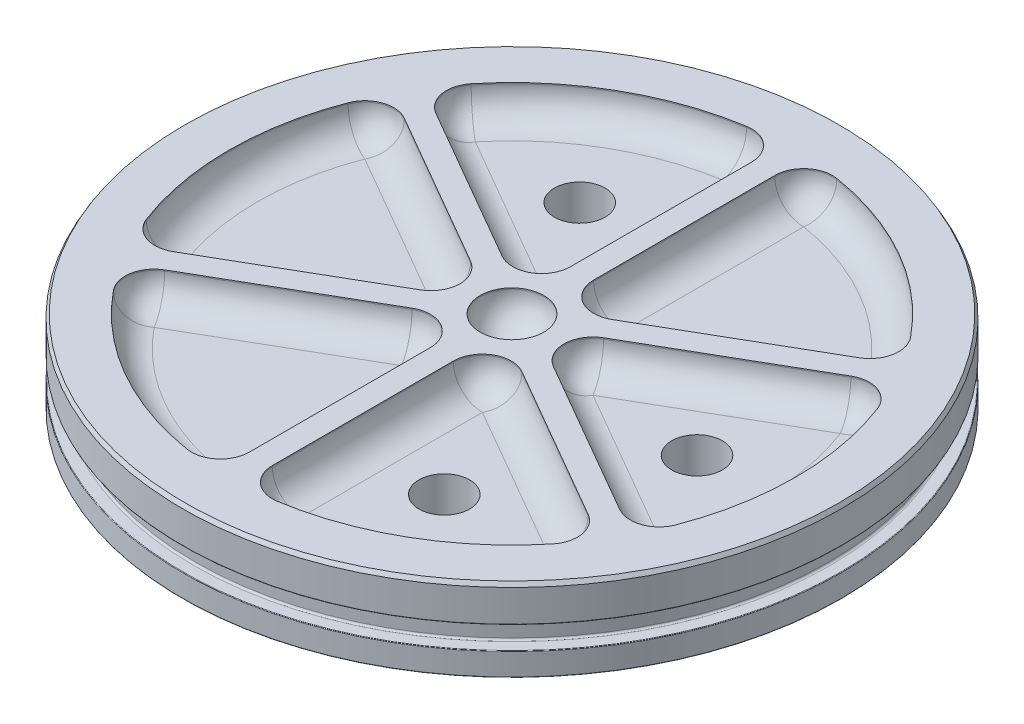
SolidWorks part; units mm, degrees
material "6061-T6 (SS)"
ref_plane "Front Plane" through (0, 0, 0) normal (0, 0, 1) x (1, 0, 0)
ref_plane "Top Plane" through (0, 0, 0) normal (0, 1, 0) x (1, 0, 0)
ref_plane "Right Plane" through (0, 0, 0) normal (1, 0, 0) x (0, 0, -1)
sketch "Sketch1" plane through (0, 0, 0) normal (0, 0, 1) x (1, 0, 0)
  line L0 (0, 48.1922) -> (0, -25.6743) construction
  line L1 (0, 0) -> (72.39, 0)
  line L2 (72.39, 0) -> (72.39, 5.08)
  line L3 (72.39, 5.08) -> (69.469, 5.08)
  line L4 (69.469, 5.08) -> (69.469, 10.0584)
  line L5 (69.469, 10.0584) -> (72.39, 10.0584)
  line L6 (72.39, 10.0584) -> (72.39, 18.034)
  line L7 (72.39, 18.034) -> (62.23, 18.034)
  line L8 (62.23, 18.034) -> (62.23, 11.43)
  line L9 (62.23, 11.43) -> (0, 11.43)
  line L10 (0, 11.43) -> (0, 0)
  dimension "D1" = 144.78
  dimension "D2" = 4.9784
  dimension "D3" = 2.921
  dimension "D5" = 11.43
  dimension "D6" = 10.16
  dimension "D4" = 18.034
  dimension "D7" = 5.08
revolve "Revolve1" add sketch "Sketch1" angle 360 about L0
sketch "Sketch6" plane through (0, 0, 0) normal (0, -1, 0) x (1, 0, 0)
  circle A0 centre (0, 0) radius 65.405
  dimension "D1" = 130.81
extrude "Boss-Extrude1" add sketch "Sketch6" along normal blind 2.54
hole_wizard "Pipe Tap Drill for 1/4 Tap - GN2" positions "Sketch2" profile "Sketch3" hole size "1/4" standard "ANSI Inch" end condition through all
sketch "Sketch2" plane through (0, 11.43, 0) normal (0, 1, 0) x (1, 0, 0)
  line L3 (-20.32, 35.1953) -> (0, 0) construction
  line L4 (0, 0) -> (40.64, 0) construction
  line L6 (0, 0) -> (20.32, -35.1953) construction
  line L7 (0, 0) -> (0, 62.23) construction
  line L8 (0, 0) -> (0, -62.23) construction
  circle A0 centre (0, 0) radius 62.23 construction
  circle A1 centre (0, 0) radius 62.23 construction
  point P41 (20.32, -35.1953)
  point P44 (-20.32, 35.1953)
  point P47 (40.64, 0)
  dimension "D1" = 40.64
  dimension "D2" = 40.64
  dimension "D3" = 40.64
  dimension "D4" = 30
  dimension "D5" = 30
sketch "Sketch3" plane through (20.32, 11.43, 35.1953) normal (1, 0, 0) x (0, 0, 1)
  line L0 (0, 0) -> (0, 13.97)
  line L1 (0, 13.97) -> (5.5626, 13.97)
  line L2 (5.5626, 13.97) -> (5.5626, 0)
  line L5 (5.5626, 0) -> (0, 0)
  line L11 (0, -6.35) -> (0, 107.95) construction
  dimension "Thru Hole Dia." = 11.1252
  dimension "Thru Hole Depth" = 13.97
fillet "CNC ID Fillet" radius 0.4064 3 edges at (-69.469, 10.0584, 0) (-69.469, 5.08, 0) (65.405, 0, 0)
fillet "CNC OD Fillet" radius 0.127 4 edges at (-72.39, 10.0584, 0) (-72.39, 5.08, 0) (65.405, -2.54, 0) (-72.39, 0, 0)
chamfer "CNC Chamfers" distance 0.508 angle 60 1 edges at (-72.39, 18.034, 0) first distance on face at (-62.23, 18.034, 0)
sketch "Sketch7" plane through (0, 18.034, 0) normal (0, 1, 0) x (1, 0, 0)
  line L0 (0, 0) -> (53.8928, -31.115) construction
  line L1 (0, 0) -> (0, -62.23) construction
  line L2 (0, 0) -> (-53.8928, -31.115) construction
  line L3 (0, 0) -> (-53.8928, 31.115) construction
  line L4 (0, 0) -> (0, 62.23) construction
  line L5 (0, 0) -> (53.8928, 31.115) construction
  line L6 (2.54, 15.3979) -> (2.54, 62.23)
  line L7 (-12.065, 9.8987) -> (-52.6228, 33.3147)
  line L8 (-14.605, -5.4993) -> (-55.1628, -28.9153)
  line L9 (-2.54, -15.3979) -> (-2.54, -62.23)
  line L10 (12.065, -9.8987) -> (52.6228, -33.3147)
  line L11 (14.605, 5.4993) -> (55.1628, 28.9153)
  line L12 (-2.54, 15.3979) -> (-2.54, 62.23)
  line L13 (-14.605, 5.4993) -> (-55.1628, 28.9153)
  line L14 (-12.065, -9.8987) -> (-52.6228, -33.3147)
  line L15 (2.54, -15.3979) -> (2.54, -62.23)
  line L16 (14.605, -5.4993) -> (55.1628, -28.9153)
  line L17 (12.065, 9.8987) -> (52.6228, 33.3147)
  line L18 (2.54, 0) -> (2.54, 62.23) construction
  line L19 (-1.27, 2.1997) -> (52.6228, 33.3147) construction
  line L20 (1.27, -2.1997) -> (55.1628, 28.9153) construction
  line L21 (1.27, 2.1997) -> (55.1628, -28.9153) construction
  line L22 (-1.27, -2.1997) -> (52.6228, -33.3147) construction
  line L23 (2.54, 0) -> (2.54, -62.23) construction
  line L24 (-2.54, 0) -> (-2.54, -62.23) construction
  line L25 (1.27, -2.1997) -> (-52.6228, -33.3147) construction
  line L26 (-1.27, 2.1997) -> (-55.1628, -28.9153) construction
  line L27 (-1.27, -2.1997) -> (-55.1628, 28.9153) construction
  line L28 (1.27, 2.1997) -> (-52.6228, 33.3147) construction
  line L29 (-2.54, 0) -> (-2.54, 62.23) construction
  line L30 (0, 0) -> (-62.23, 0) construction
  circle A0 centre (0, 0) radius 62.23 construction
  circle A1 centre (0, 0) radius 62.23
  arc A2 (2.54, 15.3979) -> (12.065, 9.8987) centre (8.89, 15.3979) ccw
  arc A3 (14.605, 5.4993) -> (14.605, -5.4993) centre (17.78, 0) ccw
  arc A4 (12.065, -9.8987) -> (2.54, -15.3979) centre (8.89, -15.3979) ccw
  arc A5 (-2.54, -15.3979) -> (-12.065, -9.8987) centre (-8.89, -15.3979) ccw
  arc A6 (-14.605, -5.4993) -> (-14.605, 5.4993) centre (-17.78, 0) ccw
  arc A7 (-12.065, 9.8987) -> (-2.54, 15.3979) centre (-8.89, 15.3979) ccw
  circle A9 centre (0, 0) radius 6.985
  point P11 (0, 0)
  circle M5 centre (0, 0) radius 62.23
  dimension "D4" = 6.35
  dimension "D6" = 13.97
  dimension "D5" = 30
  dimension "D2" = 2.54
  dimension "D3" = 2.54
  dimension "D1" = 6
extrude "Boss-Extrude2" add sketch "Sketch7" against normal up to surface (6.604 mm away) contours A7 L7 L13 A6 L8 L14 A5 L9 L15 A4 L10 L16 A3 L11 L17 A2 L6 L12 M5 region at (4.8837, 18.034, -8.4588) up to face at (20.32, 11.43, 40.7579)
fillet "Fillet1" radius 6.35 37 edges at (32.3214, 11.43, 21.5937) (5.715, 11.43, 9.8987) (34.8614, 11.43, -17.1943) (11.43, 11.43, 0) (-32.3214, 11.43, -21.5937) (-5.715, 11.43, -9.8987) (-5.715, 11.43, 9.8987) (-2.54, 11.43, 38.788) (-31.115, 11.43, 53.8928) (-32.3214, 11.43, 21.5937) (-11.43, 11.43, 0) (-34.8614, 11.43, 17.1943) (-62.23, 11.43, 0) (-34.8614, 11.43, -17.1943) (5.715, 11.43, -9.8987) (2.54, 11.43, -38.788) (31.115, 11.43, -53.8928) (32.3214, 11.43, -21.5937) (52.5779, 14.732, 33.2888) (2.54, 14.732, 62.1781) (31.115, 11.43, 53.8928) (2.54, 11.43, 38.788) (62.23, 11.43, 0) (34.8614, 11.43, 17.1943) (55.1179, 14.732, 28.8894) (55.1179, 14.732, -28.8894) (52.5779, 14.732, -33.2888) (2.54, 14.732, -62.1781) (-2.54, 14.732, 62.1781) (-52.5779, 14.732, 33.2888) (-55.1179, 14.732, 28.8894) (-52.5779, 14.732, -33.2888) (-2.54, 11.43, -38.788) (-2.54, 14.732, -62.1781) (-31.115, 11.43, -53.8928) (-55.1179, 14.732, -28.8894) (6.985, 11.43, 0)
sketch "Sketch8" plane through (0, -2.54, 0) normal (0, -1, 0) x (1, 0, 0)
  line L2 (-49.0472, -25.3844) -> (-14.605, -5.4993)
  line L3 (-14.605, 5.4993) -> (-49.0472, 25.3844)
  line L4 (-49.0472, -25.3844) -> (-14.605, -5.4993)
  line L5 (-14.605, 5.4993) -> (-49.0472, 25.3844)
  line L6 (-2.54, 15.3979) -> (-2.54, 55.1683)
  line L7 (-46.5072, 29.7839) -> (-12.065, 9.8987)
  line L8 (-2.54, 15.3979) -> (-2.54, 55.1683)
  line L9 (-46.5072, 29.7839) -> (-12.065, 9.8987)
  line L10 (12.065, 9.8987) -> (46.5072, 29.7839)
  line L11 (2.54, 55.1683) -> (2.54, 15.3979)
  line L12 (12.065, 9.8987) -> (46.5072, 29.7839)
  line L13 (2.54, 55.1683) -> (2.54, 15.3979)
  line L14 (14.605, -5.4993) -> (49.0472, -25.3844)
  line L15 (49.0472, 25.3844) -> (14.605, 5.4993)
  line L16 (14.605, -5.4993) -> (49.0472, -25.3844)
  line L17 (49.0472, 25.3844) -> (14.605, 5.4993)
  line L18 (2.54, -15.3979) -> (2.54, -55.1683)
  line L19 (46.5072, -29.7839) -> (12.065, -9.8987)
  line L20 (2.54, -15.3979) -> (2.54, -55.1683)
  line L21 (46.5072, -29.7839) -> (12.065, -9.8987)
  line L22 (-12.065, -9.8987) -> (-46.5072, -29.7839)
  line L23 (-2.54, -55.1683) -> (-2.54, -15.3979)
  line L24 (-12.065, -9.8987) -> (-46.5072, -29.7839)
  line L25 (-2.54, -55.1683) -> (-2.54, -15.3979)
  circle A0 centre (0, 0) radius 6.985 construction
  circle A1 centre (0, 0) radius 65.278
  circle A3 centre (0, 0) radius 6.985
  circle A5 centre (0, 0) radius 65.278
  arc A6 (-58.1565, 22.1449) -> (-58.1565, -22.1449) centre (0, 0) ccw
  arc A7 (-58.1565, -22.1449) -> (-49.0472, -25.3844) centre (-52.2222, -19.8852) ccw
  arc A8 (-14.605, -5.4993) -> (-14.605, 5.4993) centre (-17.78, 0) ccw
  arc A9 (-49.0472, 25.3844) -> (-58.1565, 22.1449) centre (-52.2222, 19.8852) ccw
  arc A10 (-58.1565, 22.1449) -> (-58.1565, -22.1449) centre (0, 0) ccw
  arc A11 (-58.1565, -22.1449) -> (-49.0472, -25.3844) centre (-52.2222, -19.8852) ccw
  arc A12 (-14.605, -5.4993) -> (-14.605, 5.4993) centre (-17.78, 0) ccw
  arc A13 (-49.0472, 25.3844) -> (-58.1565, 22.1449) centre (-52.2222, 19.8852) ccw
  arc A14 (-2.54, 55.1683) -> (-9.9002, 61.4374) centre (-8.89, 55.1683) ccw
  arc A15 (-9.9002, 61.4374) -> (-48.2563, 39.2926) centre (0, 0) ccw
  arc A16 (-48.2563, 39.2926) -> (-46.5072, 29.7839) centre (-43.3322, 35.2831) ccw
  arc A17 (-12.065, 9.8987) -> (-2.54, 15.3979) centre (-8.89, 15.3979) ccw
  arc A18 (-2.54, 55.1683) -> (-9.9002, 61.4374) centre (-8.89, 55.1683) ccw
  arc A19 (-9.9002, 61.4374) -> (-48.2563, 39.2926) centre (0, 0) ccw
  arc A20 (-48.2563, 39.2926) -> (-46.5072, 29.7839) centre (-43.3322, 35.2831) ccw
  arc A21 (-12.065, 9.8987) -> (-2.54, 15.3979) centre (-8.89, 15.3979) ccw
  arc A22 (46.5072, 29.7839) -> (48.2563, 39.2926) centre (43.3322, 35.2831) ccw
  arc A23 (48.2563, 39.2926) -> (9.9002, 61.4374) centre (0, 0) ccw
  arc A24 (9.9002, 61.4374) -> (2.54, 55.1683) centre (8.89, 55.1683) ccw
  arc A25 (2.54, 15.3979) -> (12.065, 9.8987) centre (8.89, 15.3979) ccw
  arc A26 (46.5072, 29.7839) -> (48.2563, 39.2926) centre (43.3322, 35.2831) ccw
  arc A27 (48.2563, 39.2926) -> (9.9002, 61.4374) centre (0, 0) ccw
  arc A28 (9.9002, 61.4374) -> (2.54, 55.1683) centre (8.89, 55.1683) ccw
  arc A29 (2.54, 15.3979) -> (12.065, 9.8987) centre (8.89, 15.3979) ccw
  arc A30 (49.0472, -25.3844) -> (58.1565, -22.1449) centre (52.2222, -19.8852) ccw
  arc A31 (58.1565, -22.1449) -> (58.1565, 22.1449) centre (0, 0) ccw
  arc A32 (58.1565, 22.1449) -> (49.0472, 25.3844) centre (52.2222, 19.8852) ccw
  arc A33 (14.605, 5.4993) -> (14.605, -5.4993) centre (17.78, 0) ccw
  arc A34 (49.0472, -25.3844) -> (58.1565, -22.1449) centre (52.2222, -19.8852) ccw
  arc A35 (58.1565, -22.1449) -> (58.1565, 22.1449) centre (0, 0) ccw
  arc A36 (58.1565, 22.1449) -> (49.0472, 25.3844) centre (52.2222, 19.8852) ccw
  arc A37 (14.605, 5.4993) -> (14.605, -5.4993) centre (17.78, 0) ccw
  arc A38 (2.54, -55.1683) -> (9.9002, -61.4374) centre (8.89, -55.1683) ccw
  arc A39 (9.9002, -61.4374) -> (48.2563, -39.2926) centre (0, 0) ccw
  arc A40 (48.2563, -39.2926) -> (46.5072, -29.7839) centre (43.3322, -35.2831) ccw
  arc A41 (12.065, -9.8987) -> (2.54, -15.3979) centre (8.89, -15.3979) ccw
  arc A42 (2.54, -55.1683) -> (9.9002, -61.4374) centre (8.89, -55.1683) ccw
  arc A43 (9.9002, -61.4374) -> (48.2563, -39.2926) centre (0, 0) ccw
  arc A44 (48.2563, -39.2926) -> (46.5072, -29.7839) centre (43.3322, -35.2831) ccw
  arc A45 (12.065, -9.8987) -> (2.54, -15.3979) centre (8.89, -15.3979) ccw
  arc A46 (-46.5072, -29.7839) -> (-48.2563, -39.2926) centre (-43.3322, -35.2831) ccw
  arc A47 (-48.2563, -39.2926) -> (-9.9002, -61.4374) centre (0, 0) ccw
  arc A48 (-9.9002, -61.4374) -> (-2.54, -55.1683) centre (-8.89, -55.1683) ccw
  arc A49 (-2.54, -15.3979) -> (-12.065, -9.8987) centre (-8.89, -15.3979) ccw
  arc A50 (-46.5072, -29.7839) -> (-48.2563, -39.2926) centre (-43.3322, -35.2831) ccw
  arc A51 (-48.2563, -39.2926) -> (-9.9002, -61.4374) centre (0, 0) ccw
  arc A52 (-9.9002, -61.4374) -> (-2.54, -55.1683) centre (-8.89, -55.1683) ccw
  arc A53 (-2.54, -15.3979) -> (-12.065, -9.8987) centre (-8.89, -15.3979) ccw
  dimension "D1" = 0
  dimension "D2" = 0
  dimension "D3" = 0
  dimension "D4" = 0
  dimension "D5" = 0
  dimension "D6" = 0
  dimension "D7" = 0
extrude "Cut-Extrude1" cut sketch "Sketch8" against normal blind 3.81 contours L8 A18 A19 A20 L9 A21 | A10 A11 L4 A12 L5 A13 | L24 A50 A51 A52 L25 A53 | L20 A42 A43 A44 L21 A45 | L16 A34 A35 A36 L17 A37 | L12 A26 A27 A28 L13 A29 | A3
fillet "Fillet2" radius 6.35 37 edges at (54.3499, 1.27, 25.8681) (62.23, 1.27, 0) (54.3499, 1.27, -25.8681) (31.8261, 1.27, -15.4419) (11.43, 1.27, 0) (4.7725, 1.27, 60.0024) (31.115, 1.27, 53.8928) (49.5774, 1.27, 34.1343) (29.2861, 1.27, 19.8413) (5.715, 1.27, 9.8987) (-5.715, 1.27, -9.8987) (-2.54, 1.27, -35.2831) (-4.7725, 1.27, -60.0024) (-31.115, 1.27, -53.8928) (-49.5774, 1.27, -34.1343) (29.2861, 1.27, -19.8413) (49.5774, 1.27, -34.1343) (31.115, 1.27, -53.8928) (4.7725, 1.27, -60.0024) (2.54, 1.27, -35.2831) (5.715, 1.27, -9.8987) (-29.2861, 1.27, 19.8413) (-49.5774, 1.27, 34.1343) (-31.115, 1.27, 53.8928) (-4.7725, 1.27, 60.0024) (-2.54, 1.27, 35.2831) (-5.715, 1.27, 9.8987) (-31.8261, 1.27, 15.4419) (-11.43, 1.27, 0) (-31.8261, 1.27, -15.4419) (-54.3499, 1.27, -25.8681) (-62.23, 1.27, 0) (-54.3499, 1.27, 25.8681) (31.8261, 1.27, 15.4419) (2.54, 1.27, 35.2831) (-29.2861, 1.27, -19.8413) (6.985, 1.27, 0)
sketch "Sketch9" plane through (0, 18.034, 0) normal (0, 1, 0) x (1, 0, 0)
  circle A0 centre (0, 0) radius 64.9299 construction
  text T0 "THIS SIDE IN                                                               FUEL BULKHEAD                                                                           RELEVANT EXPERIENCE                                "
sketch "Sketch11" plane through (0, 1.27, 0) normal (0, -1, 0) x (1, 0, 0)
  arc A0 (-43.7432, -35.6178) -> (-8.9743, -55.6917) centre (0, 0) ccw construction
  arc A1 (52.7176, -20.0738) -> (52.7176, 20.0738) centre (0, 0) ccw construction
  arc A2 (43.7432, 35.6178) -> (8.9743, 55.6917) centre (0, 0) ccw construction
  arc A3 (-43.7432, -35.6178) -> (-8.9743, -55.6917) centre (0, 0) ccw construction
  arc A4 (52.7176, -20.0738) -> (52.7176, 20.0738) centre (0, 0) ccw construction
  arc A5 (43.7432, 35.6178) -> (8.9743, 55.6917) centre (0, 0) ccw construction
  arc A6 (50.3438, -19.17) -> (50.3438, 19.17) centre (0, 0) ccw construction
  arc A7 (41.7736, 34.0141) -> (8.5702, 53.184) centre (0, 0) ccw construction
  arc A8 (-41.7736, -34.0141) -> (-8.5702, -53.184) centre (0, 0) ccw construction
  text T0 "FILL" font "Century Gothic" height in points 18
  text T1 "GN2" font "Century Gothic" height in points 18
  text T2 "VENT" font "Century Gothic" height in points 18
  dimension "D1" = 2.54
sketch "Sketch12" plane through (0, -2.54, 0) normal (0, -1, 0) x (1, 0, 0)
  line L0 (0, 0) -> (0, 64.9299) construction
  line L1 (1.397, 0) -> (1.397, 64.9299) construction
  circle A0 centre (0, 0) radius 64.9299 construction
  text T0 "THIS SIDE OUT" font "Century Gothic" height in points 11
  dimension "D1" = 1.397
equation "\"D3@Sketch1\"=(5.7-5.47)/2"
